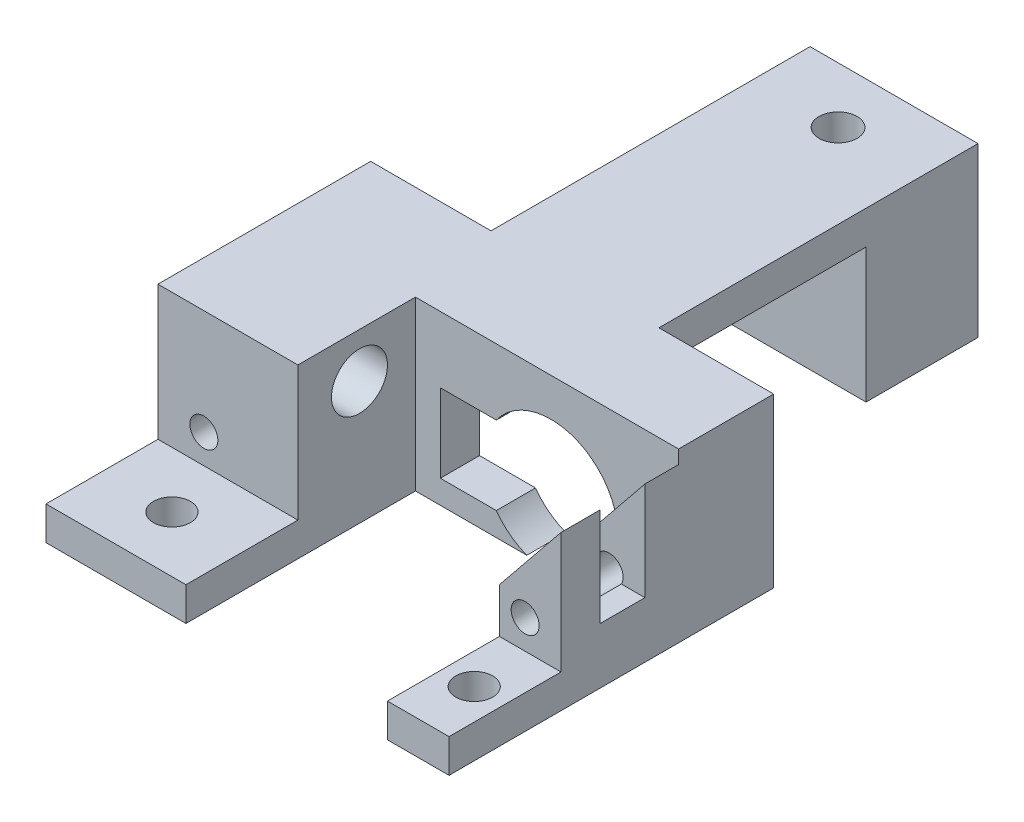
SolidWorks part; units mm, degrees
ref_plane "Ebene vorne" through (0, 0, 0) normal (0, 0, 1) x (1, 0, 0)
ref_plane "Ebene oben" through (0, 0, 0) normal (0, 1, 0) x (1, 0, 0)
ref_plane "Ebene rechts" through (0, 0, 0) normal (1, 0, 0) x (0, 0, -1)
sketch "Sketch1" plane through (0, 0, 0) normal (0, 1, 0) x (1, 0, 0)
  line L1 (0, 0) -> (36, 0)
  line L2 (0, 0) -> (0, 20)
  line L3 (0, 20) -> (36, 20)
  line L4 (36, 0) -> (36, 20)
  dimension "D1" = 36
  dimension "D2" = 20
extrude "Boss-Extrude1" add sketch "Sketch1" along normal blind 15
sketch "Sketch2" plane through (0, 0, 0) normal (-1, 0, 0) x (0, 0, 1)
  line L0 (0, 15) -> (0, 0) construction
  line L1 (-20, 0) -> (0, 0) construction
  circle A0 centre (-5.5, 11) radius 1.15
  circle A1 centre (-5.5, 11) radius 2.5
  dimension "D1" = 2.3
  dimension "D4" = 5
  dimension "D2" = 5.5
  dimension "D3" = 11
extrude "Cut-Extrude1" cut sketch "Sketch2" against normal blind 15 contours A0
sketch "Sketch3" plane through (0, 0, 0) normal (0, 0, 1) x (1, 0, 0)
  line L0 (0, 15) -> (36, 15) construction
  line L1 (12.5, 15) -> (30.5, 15)
  line L2 (12.5, 15) -> (12.5, 0)
  line L3 (12.5, 0) -> (30.5, 0)
  line L4 (30.5, 15) -> (30.5, 0)
  line L5 (0, 0) -> (36, 0) construction
  line L7 (36, 15) -> (36, 0) construction
  dimension "D1" = 18
  dimension "D2" = 5.5
extrude "Cut-Extrude2" cut sketch "Sketch3" against normal blind 10.5
sketch "Sketch4" plane through (0, 0, -20) normal (0, 0, -1) x (-1, 0, 0)
  line L0 (-36, 0) -> (0, 0) construction
  line L1 (-30.5, 0) -> (-6, 0)
  line L2 (-30.5, 0) -> (-30.5, 12)
  line L3 (-30.5, 12) -> (-6, 12)
  line L4 (-6, 0) -> (-6, 12)
  line L5 (0, 15) -> (0, 0) construction
  dimension "D1" = 12
  dimension "D2" = 24.5
  dimension "D3" = 6
extrude "Cut-Extrude4" cut sketch "Sketch4" against normal blind 6
sketch "Sketch6" plane through (0, 0, -20) normal (0, 0, -1) x (-1, 0, 0)
  line L0 (-36, 0) -> (-30.5, 0) construction
  line L1 (-6, 0) -> (-6, 12) construction
  circle A0 centre (-32.8, 5.6) radius 1.25
  circle A1 centre (-4.1, 5.6) radius 1.25
  point P9 (-6, 6)
  dimension "D1" = 2.5
  dimension "D2" = 2.5
  dimension "D3" = 28.7
  dimension "D4" = 5.6
  dimension "D5" = 1.9
extrude "Cut-Extrude6" cut sketch "Sketch6" against normal through all both and the other way through all
sketch "Sketch5" plane through (0, 0, -10.5) normal (0, 0, 1) x (1, 0, 0)
  line L0 (30.5, 0) -> (6, 0) construction
  circle A0 centre (24.6, 5.6) radius 3.25
  circle A1 centre (32.8, 5.6) radius 1.25 construction
  dimension "D1" = 6.5
  dimension "D2" = 8.2
  dimension "D3" = 5.6
extrude "Cut-Extrude5" cut sketch "Sketch5" against normal up to surface (3.5 mm away) up to face at (18.25, 6, -14)
chamfer "Chamfer3" distance 8 angle 39 1 edges at (30.5, 15, -5.25) first distance on face at (30.5, 7.5, -5.25)
sketch "Sketch14" plane through (36, 0, 0) normal (1, 0, 0) x (0, 0, -1)
  line L0 (3.5, 13.7919) -> (3.5, 5)
  line L1 (10.5, 13.7919) -> (0, 13.7919) construction
  line L2 (3.5, 5) -> (7.5, 5)
  line L3 (7.5, 5) -> (7.5, 13.7919)
  line L4 (7.5, 13.7919) -> (3.5, 13.7919)
  line L5 (0, 0) -> (20, 0) construction
  line L6 (0, 13.7919) -> (0, 0) construction
  line L7 (5.5, 13.7919) -> (5.5, 5) construction
  dimension "D1" = 5
  dimension "D2" = 3.5
  dimension "D3" = 4
extrude "Cut-Extrude11" cut sketch "Sketch14" against normal up to surface (5.5 mm away) up to face at (30.5, 3.5, -5.25)
extrude "Cut-Extrude3" cut sketch "Sketch2<3>" against normal up to surface (12.5 mm away) from offset 6 contours A1 up to face at (12.5, 7.5, -5.25) offset against normal yes
sketch "Sketch2<3>" plane through (0, 0, 0) normal (-1, 0, 0) x (0, 0, 1) same geometry as "Sketch2"
sketch "Sketch7" plane through (0, 0, -20) normal (0, 0, -1) x (-1, 0, 0)
  line L0 (-36, 15) -> (0, 15) construction
  line L1 (-25.75, 15) -> (-10.75, 15)
  line L2 (-25.75, 15) -> (-25.75, 12)
  line L3 (-25.75, 12) -> (-10.75, 12)
  line L4 (-10.75, 15) -> (-10.75, 12)
  line L5 (-6, 12) -> (-30.5, 12) construction
  line L6 (-18.25, 0) -> (-18.25, 15) construction
  line L7 (-30.5, 0) -> (-6, 0) construction
  dimension "D1" = 15
extrude "Boss-Extrude2" add sketch "Sketch7" along normal blind 17.5
sketch "Sketch8" plane through (0, 0, -37.5) normal (0, 0, -1) x (-1, 0, 0)
  line L0 (-30.5, 0) -> (-6, 0) construction
  line L1 (-25.75, 15) -> (-10.75, 15)
  line L2 (-25.75, 15) -> (-25.75, 0)
  line L3 (-25.75, 0) -> (-10.75, 0)
  line L4 (-10.75, 15) -> (-10.75, 0)
  line L5 (-10.75, 12) -> (-10.75, 15) construction
extrude "Boss-Extrude3" add sketch "Sketch8" along normal blind 10
sketch "Sketch9" plane through (0, 15, 0) normal (0, 1, 0) x (1, 0, 0)
  line L0 (18.25, 47.5) -> (18.25, 15.6733) construction
  line L1 (10.75, 47.5) -> (25.75, 47.5) construction
  circle A0 centre (18.25, 42.5) radius 1.7
  dimension "D1" = 3.4
  dimension "D2" = 5
extrude "Cut-Extrude7" cut sketch "Sketch9" against normal blind 20
sketch "Sketch10" plane through (0, 0, 0) normal (0, 0, 1) x (1, 0, 0)
  line L0 (0, 15) -> (0, 0) construction
  line L1 (0, 3) -> (12.5, 3)
  line L2 (0, 3) -> (0, 0)
  line L3 (0, 0) -> (12.5, 0)
  line L4 (12.5, 3) -> (12.5, 0)
  line L5 (30.5, 0) -> (30.5, 7) construction
  line L6 (30.5, 3) -> (36, 3)
  line L7 (30.5, 3) -> (30.5, 0)
  line L8 (30.5, 0) -> (36, 0)
  line L9 (36, 3) -> (36, 0)
  dimension "D1" = 3
  dimension "D2" = 3
extrude "Boss-Extrude4" add sketch "Sketch10" along normal blind 10
sketch "Sketch11" plane through (0, 3, 0) normal (0, 1, 0) x (1, 0, 0)
  line L0 (0, -5) -> (36, -5) construction
  line L1 (0, -10) -> (0, 0) construction
  line L2 (36, -10) -> (36, 0) construction
  line L3 (6.25, 0) -> (6.25, -10) construction
  line L4 (0, 0) -> (12.5, 0) construction
  line L5 (12.5, -10) -> (0, -10) construction
  line L6 (33.25, 0) -> (33.25, -10) construction
  line L7 (36, 0) -> (30.5, 0) construction
  line L8 (36, -10) -> (30.5, -10) construction
  circle A0 centre (6.25, -5) radius 1.65
  circle A1 centre (33.25, -5) radius 1.65
  dimension "D1" = 3.3
  dimension "D2" = 3.3
extrude "Cut-Extrude8" cut sketch "Sketch11" against normal blind 10
sketch "Sketch12" plane through (0, 0, -10.5) normal (0, 0, 1) x (1, 0, 0)
  line L0 (14.7266, 9.1) -> (14.7266, 2.1)
  line L1 (14.7266, 2.1) -> (19.7266, 2.1)
  line L2 (14.7266, 9.1) -> (19.7266, 9.1)
  line L3 (24.6, 5.6) -> (9.6083, 5.6) construction
  arc A0 (19.7266, 2.1) -> (19.7266, 9.1) centre (24.6, 5.6) ccw
  dimension "D1" = 12
  dimension "D2" = 7
  dimension "D3" = 5
extrude "Cut-Extrude9" cut sketch "Sketch12" against normal up to surface (3.5 mm away) contours L2 A0 L1 L0 up to face at (27.85, 5.6, -14)
sketch "Sketch13" plane through (0, 0, -20) normal (0, 0, -1) x (-1, 0, 0)
  line L0 (-36, 0) -> (-36, 15)
  line L1 (-36, 15) -> (-25.75, 15)
  line L2 (-25.75, 15) -> (-25.75, 0)
  line L3 (-25.75, 0) -> (-36, 0)
  line L4 (-36, 0) -> (-35.7803, 0.1298)
  line L5 (-10.75, 15) -> (0, 15)
  line L6 (0, 15) -> (0, 0)
  line L7 (0, 0) -> (-10.75, 0)
  line L8 (-10.75, 0) -> (-10.75, 15)
  circle M1 centre (-32.8, 5.6) radius 1.25
  line M2 (-25.75, 12) -> (-25.75, 15)
  line M3 (-25.75, 15) -> (-36, 15)
  line M4 (-36, 15) -> (-36, 0)
  line M5 (-36, 0) -> (-30.5, 0)
  line M6 (-30.5, 0) -> (-30.5, 12)
  line M7 (-30.5, 12) -> (-25.75, 12)
extrude "Cut-Extrude10" cut sketch "Sketch13" against normal blind 1 contours M7 M2 M3 M4 M5 M6 M1 | L8 L7 L6 L5 region at (32.4789, 8.5325, -20) region at (5.375, 7.5, -20)
